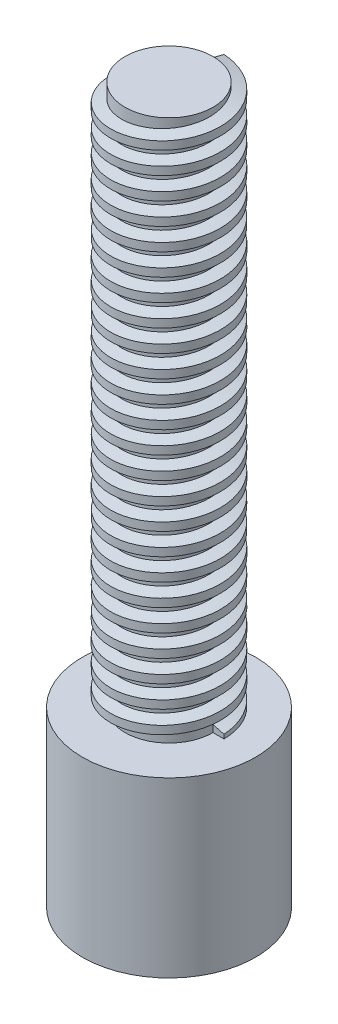
SolidWorks part; units mm, degrees
ref_plane "Front Plane" through (0, 0, 0) normal (0, 0, 1) x (1, 0, 0)
ref_plane "Top Plane" through (0, 0, 0) normal (0, 1, 0) x (1, 0, 0)
ref_plane "Right Plane" through (0, 0, 0) normal (1, 0, 0) x (0, 0, -1)
sketch "Sketch1" plane through (0, 0, 0) normal (0, 1, 0) x (1, 0, 0)
  circle A0 centre (0, 0) radius 12.7
  dimension "D1" = 25.4
extrude "Boss-Extrude1" add sketch "Sketch1" along normal blind 125 contours A0
sketch "Sketch5" plane through (0, 0, 0) normal (0, -1, 0) x (1, 0, 0)
  circle A0 centre (0, 0) radius 12.7 construction
  circle A1 centre (0, 0) radius 12.7
curve "Helix/Spiral1" pitch 5.08 height 123.19 radius 12.7 centre (0, 0, 0) axis (0, 1, 0) start towards (1, 0, 0)
sketch "Sketch9" plane through (0, 0, 0) normal (0, -1, 0) x (1, 0, 0)
  circle A0 centre (0, 0) radius 12.7 construction
  circle A1 centre (0, 0) radius 12.7
  circle A2 centre (0, 0) radius 10.16
  dimension "D1" = 2.54
extrude "Cut-Extrude1" cut sketch "Sketch9" against normal blind 285.4
sketch "Sketch10" plane through (0, 0, 0) normal (0, 0, 1) x (1, 0, 0)
  line L0 (-10.16, 51.7416) -> (-10.16, 54.9384)
  line L1 (-10.16, 51.7416) -> (-12.7, 52.3984)
  line L2 (-12.7, 52.3984) -> (-12.7, 54.2816)
  line L3 (-12.7, 54.2816) -> (-10.16, 54.9384)
  line L4 (-10.16, 125) -> (-10.16, 0) construction
  line L5 (-12.7, 53.34) -> (15.24, 53.34) construction
  line L6 (-11.43, 54.61) -> (-11.43, 52.07) construction
  spline S0 degree 3 poles (12.7, 0) (12.7, 0.1052) (12.0387, 0.3178) (9.214, 0.6349) (4.9866, 0.9525) (0, 1.27) (-4.9866, 1.5875) (-9.214, 1.905) (-12.0387, 2.2225) (-13.0306, 2.54) (-12.0387, 2.8575) (-9.214, 3.175) (-4.9866, 3.4925) (0, 3.81) (4.9866, 4.1275) (9.214, 4.445) (12.0387, 4.7625) (13.0306, 5.08) (12.0387, 5.3975) (9.214, 5.715) (4.9866, 6.0325) (0, 6.35) (-4.9866, 6.6675) (-9.214, 6.985) (-12.0387, 7.3025) (-13.0306, 7.62) (-12.0387, 7.9375) (-9.214, 8.255) (-4.9866, 8.5725) (0, 8.89) (4.9866, 9.2075) (9.214, 9.525) (12.0387, 9.8425) (13.0306, 10.16) (12.0387, 10.4775) (9.214, 10.795) (4.9866, 11.1125) (0, 11.43) (-4.9866, 11.7475) (-9.214, 12.065) (-12.0387, 12.3825) (-13.0306, 12.7) (-12.0387, 13.0175) (-9.214, 13.335) (-4.9866, 13.6525) (0, 13.97) (4.9866, 14.2875) (9.214, 14.605) (12.0387, 14.9225) (13.0306, 15.24) (12.0387, 15.5575) (9.214, 15.875) (4.9866, 16.1925) (0, 16.51) (-4.9866, 16.8275) (-9.214, 17.145) (-12.0387, 17.4625) (-13.0306, 17.78) (-12.0387, 18.0975) (-9.214, 18.415) (-4.9866, 18.7325) (0, 19.05) (4.9866, 19.3675) (9.214, 19.685) (12.0387, 20.0025) (13.0306, 20.32) (12.0387, 20.6375) (9.214, 20.955) (4.9866, 21.2725) (0, 21.59) (-4.9866, 21.9075) (-9.214, 22.225) (-12.0387, 22.5425) (-13.0306, 22.86) (-12.0387, 23.1775) (-9.214, 23.495) (-4.9866, 23.8125) (0, 24.13) (4.9866, 24.4475) (9.214, 24.765) (12.0387, 25.0825) (13.0306, 25.4) (12.0387, 25.7175) (9.214, 26.035) (4.9866, 26.3525) (0, 26.67) (-4.9866, 26.9875) (-9.214, 27.305) (-12.0387, 27.6225) (-13.0306, 27.94) (-12.0387, 28.2575) (-9.214, 28.575) (-4.9866, 28.8925) (0, 29.21) (4.9866, 29.5275) (9.214, 29.845) (12.0387, 30.1625) (13.0306, 30.48) (12.0387, 30.7975) (9.214, 31.115) (4.9866, 31.4325) (0, 31.75) (-4.9866, 32.0675) (-9.214, 32.385) (-12.0387, 32.7025) (-13.0306, 33.02) (-12.0387, 33.3375) (-9.214, 33.655) (-4.9866, 33.9725) (0, 34.29) (4.9866, 34.6075) (9.214, 34.925) (12.0387, 35.2425) (13.0306, 35.56) (12.0387, 35.8775) (9.214, 36.195) (4.9866, 36.5125) (0, 36.83) (-4.9866, 37.1475) (-9.214, 37.465) (-12.0387, 37.7825) (-13.0306, 38.1) (-12.0387, 38.4175) (-9.214, 38.735) (-4.9866, 39.0525) (0, 39.37) (4.9866, 39.6875) (9.214, 40.005) (12.0387, 40.3225) (13.0306, 40.64) (12.0387, 40.9575) (9.214, 41.275) (4.9866, 41.5925) (0, 41.91) (-4.9866, 42.2275) (-9.214, 42.545) (-12.0387, 42.8625) (-13.0306, 43.18) (-12.0387, 43.4975) (-9.214, 43.815) (-4.9866, 44.1325) (0, 44.45) (4.9866, 44.7675) (9.214, 45.085) (12.0387, 45.4025) (13.0306, 45.72) (12.0387, 46.0375) (9.214, 46.355) (4.9866, 46.6725) (0, 46.99) (-4.9866, 47.3075) (-9.214, 47.625) (-12.0387, 47.9425) (-13.0306, 48.26) (-12.0387, 48.5775) (-9.214, 48.895) (-4.9866, 49.2125) (0, 49.53) (4.9866, 49.8475) (9.214, 50.165) (12.0387, 50.4825) (13.0306, 50.8) (12.0387, 51.1175) (9.214, 51.435) (4.9866, 51.7525) (0, 52.07) (-4.9866, 52.3875) (-9.214, 52.705) (-12.0387, 53.0225) (-13.0306, 53.34) (-12.0387, 53.6575) (-9.214, 53.975) (-4.9866, 54.2925) (0, 54.61) (4.9866, 54.9275) (9.214, 55.245) (12.0387, 55.5625) (13.0306, 55.88) (12.0387, 56.1975) (9.214, 56.515) (4.9866, 56.8325) (0, 57.15) (-4.9866, 57.4675) (-9.214, 57.785) (-12.0387, 58.1025) (-13.0306, 58.42) (-12.0387, 58.7375) (-9.214, 59.055) (-4.9866, 59.3725) (0, 59.69) (4.9866, 60.0075) (9.214, 60.325) (12.0387, 60.6425) (13.0306, 60.96) (12.0387, 61.2775) (9.214, 61.595) (4.9866, 61.9125) (0, 62.23) (-4.9866, 62.5475) (-9.214, 62.865) (-12.0387, 63.1825) (-13.0306, 63.5) (-12.0387, 63.8175) (-9.214, 64.135) (-4.9866, 64.4525) (0, 64.77) (4.9866, 65.0875) (9.214, 65.405) (12.0387, 65.7225) (13.0306, 66.04) (12.0387, 66.3575) (9.214, 66.675) (4.9866, 66.9925) (0, 67.31) (-4.9866, 67.6275) (-9.214, 67.945) (-12.0387, 68.2625) (-13.0306, 68.58) (-12.0387, 68.8975) (-9.214, 69.215) (-4.9866, 69.5325) (0, 69.85) (4.9866, 70.1675) (9.214, 70.485) (12.0387, 70.8025) (13.0306, 71.12) (12.0387, 71.4375) (9.214, 71.755) (4.9866, 72.0725) (0, 72.39) (-4.9866, 72.7075) (-9.214, 73.025) (-12.0387, 73.3425) (-13.0306, 73.66) (-12.0387, 73.9775) (-9.214, 74.295) (-4.9866, 74.6125) (0, 74.93) (4.9866, 75.2475) (9.214, 75.565) (12.0387, 75.8825) (13.0306, 76.2) (12.0387, 76.5175) (9.214, 76.835) (4.9866, 77.1525) (0, 77.47) (-4.9866, 77.7875) (-9.214, 78.105) (-12.0387, 78.4225) (-13.0306, 78.74) (-12.0387, 79.0575) (-9.214, 79.375) (-4.9866, 79.6925) (0, 80.01) (4.9866, 80.3275) (9.214, 80.645) (12.0387, 80.9625) (13.0306, 81.28) (12.0387, 81.5975) (9.214, 81.915) (4.9866, 82.2325) (0, 82.55) (-4.9866, 82.8675) (-9.214, 83.185) (-12.0387, 83.5025) (-13.0306, 83.82) (-12.0387, 84.1375) (-9.214, 84.455) (-4.9866, 84.7725) (0, 85.09) (4.9866, 85.4075) (9.214, 85.725) (12.0387, 86.0425) (13.0306, 86.36) (12.0387, 86.6775) (9.214, 86.995) (4.9866, 87.3125) (0, 87.63) (-4.9866, 87.9475) (-9.214, 88.265) (-12.0387, 88.5825) (-13.0306, 88.9) (-12.0387, 89.2175) (-9.214, 89.535) (-4.9866, 89.8525) (0, 90.17) (4.9866, 90.4875) (9.214, 90.805) (12.0387, 91.1225) (13.0306, 91.44) (12.0387, 91.7575) (9.214, 92.075) (4.9866, 92.3925) (0, 92.71) (-4.9866, 93.0275) (-9.214, 93.345) (-12.0387, 93.6625) (-13.0306, 93.98) (-12.0387, 94.2975) (-9.214, 94.615) (-4.9866, 94.9325) (0, 95.25) (4.9866, 95.5675) (9.214, 95.885) (12.0387, 96.2025) (13.0306, 96.52) (12.0387, 96.8375) (9.214, 97.155) (4.9866, 97.4725) (0, 97.79) (-4.9866, 98.1075) (-9.214, 98.425) (-12.0387, 98.7425) (-13.0306, 99.06) (-12.0387, 99.3775) (-9.214, 99.695) (-4.9866, 100.0125) (0, 100.33) (4.9866, 100.6475) (9.214, 100.965) (12.0387, 101.2825) (13.0306, 101.6) (12.0387, 101.9175) (9.214, 102.235) (4.9866, 102.5525) (0, 102.87) (-4.9866, 103.1875) (-9.214, 103.505) (-12.0387, 103.8225) (-13.0306, 104.14) (-12.0387, 104.4575) (-9.214, 104.775) (-4.9866, 105.0925) (0, 105.41) (4.9866, 105.7275) (9.214, 106.045) (12.0387, 106.3625) (13.0306, 106.68) (12.0387, 106.9975) (9.214, 107.315) (4.9866, 107.6325) (0, 107.95) (-4.9866, 108.2675) (-9.214, 108.585) (-12.0387, 108.9025) (-13.0306, 109.22) (-12.0387, 109.5375) (-9.214, 109.855) (-4.9866, 110.1725) (0, 110.49) (4.9866, 110.8075) (9.214, 111.125) (12.0387, 111.4425) (13.0306, 111.76) (12.0387, 112.0775) (9.214, 112.395) (4.9866, 112.7125) (0, 113.03) (-4.9866, 113.3475) (-9.214, 113.665) (-12.0387, 113.9825) (-13.0306, 114.3) (-12.0387, 114.6175) (-9.214, 114.935) (-4.9866, 115.2525) (0, 115.57) (4.9866, 115.8875) (9.214, 116.205) (12.0387, 116.5225) (13.0306, 116.84) (12.0387, 117.1575) (9.214, 117.475) (4.9866, 117.7925) (0, 118.11) (-4.9866, 118.4275) (-9.214, 118.745) (-12.0387, 119.0625) (-13.0306, 119.38) (-12.0387, 119.6975) (-9.214, 120.015) (-4.9866, 120.3325) (0, 120.65) (4.9866, 120.9675) (9.214, 121.285) (12.0388, 121.6025) (13.0305, 121.92) (12.0391, 122.2375) (9.2128, 122.5551) (4.9914, 122.8722) (1.6518, 123.0848) (0, 123.19) knots 0 0 0 0 0.002577 0.005155 0.007732 0.010309 0.012887 0.015464 0.018041 0.020619 0.023196 0.025773 0.028351 0.030928 0.033505 0.036082 0.03866 0.041237 0.043814 0.046392 0.048969 0.051546 0.054124 0.056701 0.059278 0.061856 0.064433 0.06701 0.069588 0.072165 0.074742 0.07732 0.079897 0.082474 0.085052 0.087629 0.090206 0.092784 0.095361 0.097938 0.100515 0.103093 0.10567 0.108247 0.110825 0.113402 0.115979 0.118557 0.121134 0.123711 0.126289 0.128866 0.131443 0.134021 0.136598 0.139175 0.141753 0.14433 0.146907 0.149485 0.152062 0.154639 0.157216 0.159794 0.162371 0.164948 0.167526 0.170103 0.17268 0.175258 0.177835 0.180412 0.18299 0.185567 0.188144 0.190722 0.193299 0.195876 0.198454 0.201031 0.203608 0.206186 0.208763 0.21134 0.213918 0.216495 0.219072 0.221649 0.224227 0.226804 0.229381 0.231959 0.234536 0.237113 0.239691 0.242268 0.244845 0.247423 0.25 0.252577 0.255155 0.257732 0.260309 0.262887 0.265464 0.268041 0.270619 0.273196 0.275773 0.278351 0.280928 0.283505 0.286082 0.28866 0.291237 0.293814 0.296392 0.298969 0.301546 0.304124 0.306701 0.309278 0.311856 0.314433 0.31701 0.319588 0.322165 0.324742 0.32732 0.329897 0.332474 0.335052 0.337629 0.340206 0.342784 0.345361 0.347938 0.350515 0.353093 0.35567 0.358247 0.360825 0.363402 0.365979 0.368557 0.371134 0.373711 0.376289 0.378866 0.381443 0.384021 0.386598 0.389175 0.391753 0.39433 0.396907 0.399485 0.402062 0.404639 0.407216 0.409794 0.412371 0.414948 0.417526 0.420103 0.42268 0.425258 0.427835 0.430412 0.43299 0.435567 0.438144 0.440722 0.443299 0.445876 0.448454 0.451031 0.453608 0.456186 0.458763 0.46134 0.463918 0.466495 0.469072 0.471649 0.474227 0.476804 0.479381 0.481959 0.484536 0.487113 0.489691 0.492268 0.494845 0.497423 0.5 0.502577 0.505155 0.507732 0.510309 0.512887 0.515464 0.518041 0.520619 0.523196 0.525773 0.528351 0.530928 0.533505 0.536082 0.53866 0.541237 0.543814 0.546392 0.548969 0.551546 0.554124 0.556701 0.559278 0.561856 0.564433 0.56701 0.569588 0.572165 0.574742 0.57732 0.579897 0.582474 0.585052 0.587629 0.590206 0.592784 0.595361 0.597938 0.600515 0.603093 0.60567 0.608247 0.610825 0.613402 0.615979 0.618557 0.621134 0.623711 0.626289 0.628866 0.631443 0.634021 0.636598 0.639175 0.641753 0.64433 0.646907 0.649485 0.652062 0.654639 0.657216 0.659794 0.662371 0.664948 0.667526 0.670103 0.67268 0.675258 0.677835 0.680412 0.68299 0.685567 0.688144 0.690722 0.693299 0.695876 0.698454 0.701031 0.703608 0.706186 0.708763 0.71134 0.713918 0.716495 0.719072 0.721649 0.724227 0.726804 0.729381 0.731959 0.734536 0.737113 0.739691 0.742268 0.744845 0.747423 0.75 0.752577 0.755155 0.757732 0.760309 0.762887 0.765464 0.768041 0.770619 0.773196 0.775773 0.778351 0.780928 0.783505 0.786082 0.78866 0.791237 0.793814 0.796392 0.798969 0.801546 0.804124 0.806701 0.809278 0.811856 0.814433 0.81701 0.819588 0.822165 0.824742 0.82732 0.829897 0.832474 0.835052 0.837629 0.840206 0.842784 0.845361 0.847938 0.850515 0.853093 0.85567 0.858247 0.860825 0.863402 0.865979 0.868557 0.871134 0.873711 0.876289 0.878866 0.881443 0.884021 0.886598 0.889175 0.891753 0.89433 0.896907 0.899485 0.902062 0.904639 0.907216 0.909794 0.912371 0.914948 0.917526 0.920103 0.92268 0.925258 0.927835 0.930412 0.93299 0.935567 0.938144 0.940722 0.943299 0.945876 0.948454 0.951031 0.953608 0.956186 0.958763 0.96134 0.963918 0.966495 0.969072 0.971649 0.974227 0.976804 0.979381 0.981959 0.984536 0.987113 0.989691 0.992268 0.994845 0.997423 1 1 1 1 construction
  dimension "D1" = 2.54
  dimension "D2" = 2.54
  dimension "D3" = 14.5
  dimension "D4" = 14.5
sweep "Sweep1" add profiles "Sketch10" path "Helix/Spiral1"
sketch "Sketch2" plane through (0, 0, 0) normal (0, -1, 0) x (1, 0, 0)
  circle A0 centre (0, 0) radius 20
extrude "Boss-Extrude2" add sketch "Sketch2" along normal blind 40
sketch "Sketch11" plane through (0, -40, 0) normal (0, -1, 0) x (1, 0, 0)
  line L0 (-2.9687, -3.9688) -> (-3.9687, -2.9688)
  line L1 (2.9688, -3.9688) -> (-2.9687, -3.9688)
  line L2 (3.9688, -2.9688) -> (3.9688, 2.9687)
  line L3 (2.9688, 3.9687) -> (-2.9687, 3.9687)
  line L4 (-3.9687, -2.9688) -> (-3.9687, 2.9688)
  line L5 (3.9688, -3.9688) -> (-3.9687, 3.9687) construction
  line L6 (3.9688, 3.9687) -> (-3.9687, -3.9688) construction
  line L7 (2.9688, -3.9688) -> (3.9688, -2.9688)
  line L8 (3.9688, 2.9687) -> (2.9688, 3.9687)
  line L9 (-2.9687, 3.9687) -> (-3.9687, 2.9688)
  point P0 (0, 0)
  point P1 (0, 0)
  dimension "D1" = 7.9375
  dimension "D2" = 7.9375
  dimension "D3" = 1
  dimension "D4" = 45
  dimension "D5" = 1
  dimension "D6" = 45
  dimension "D7" = 1
  dimension "D8" = 45
  dimension "D9" = 1
  dimension "D10" = 45
extrude "Cut-Extrude2" cut sketch "Sketch11" against normal blind 19.05
fillet "Fillet1" radius 1 8 edges at (3.4688, -40, 3.4687) (0, -40, 3.9687) (-3.4687, -40, 3.4688) (-3.9687, -40, 0) (-3.4687, -40, -3.4688) (0, -40, -3.9688) (3.4688, -40, -3.4688) (3.9688, -40, 0)
